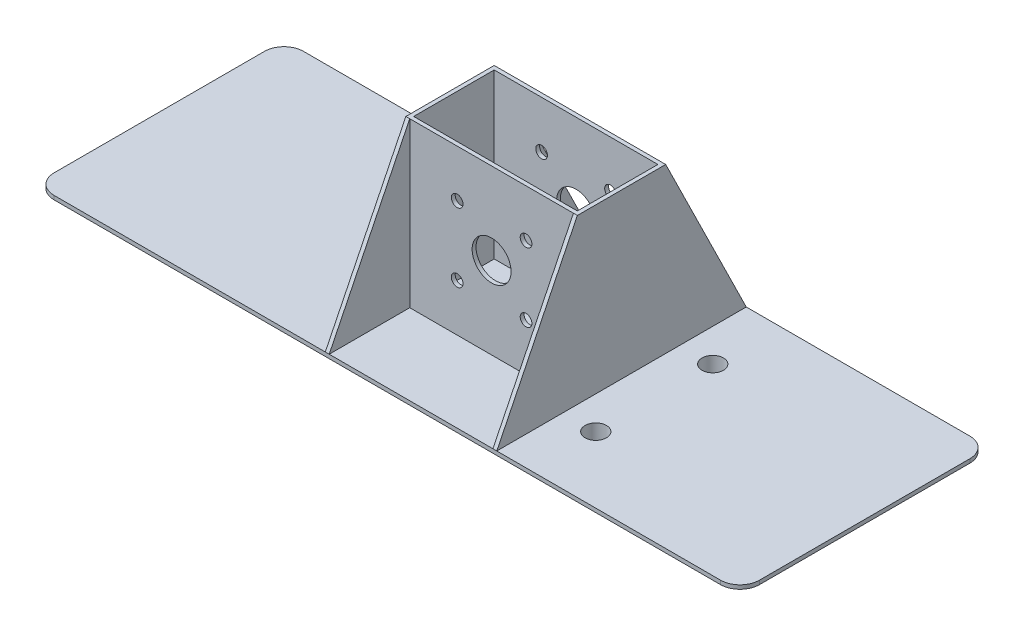
SolidWorks part; units mm, degrees
material "ABS"
ref_plane "Front Plane" through (0, 0, 0) normal (0, 0, 1) x (1, 0, 0)
ref_plane "Top Plane" through (0, 0, 0) normal (0, 1, 0) x (1, 0, 0)
ref_plane "Right Plane" through (0, 0, 0) normal (1, 0, 0) x (0, 0, -1)
sketch "Sketch1" plane through (0, 0, 0) normal (0, 1, 0) x (1, 0, 0)
  line L1 (85.5, 32) -> (-85.5, 32)
  line L2 (90.5, 27) -> (90.5, -27)
  line L3 (85.5, -32) -> (-85.5, -32)
  line L4 (-90.5, 27) -> (-90.5, -27)
  line L5 (90.5, 32) -> (-90.5, -32) construction
  line L6 (90.5, -32) -> (-90.5, 32) construction
  arc A0 (85.5, 32) -> (90.5, 27) centre (85.5, 27) cw
  arc A1 (90.5, -27) -> (85.5, -32) centre (85.5, -27) cw
  arc A2 (-85.5, -32) -> (-90.5, -27) centre (-85.5, -27) cw
  arc A3 (-85.5, 32) -> (-90.5, 27) centre (-85.5, 27) ccw
  point P0 (0, 0)
  dimension "D1" = 5
  dimension "D2" = 181
  dimension "D3" = 64
extrude "Boss-Extrude1" add sketch "Sketch1" along normal blind 1
sketch "Sketch2" plane through (0, 1, 0) normal (0, 1, 0) x (1, 0, 0)
  line L0 (-90.5, 0) -> (90.5, 0) construction
  line L1 (-90.5, 27) -> (-90.5, -27) construction
  line L2 (90.5, -27) -> (90.5, 27) construction
  circle A0 centre (36.5, -15) radius 2.75
  circle A1 centre (36.5, 15) radius 2.75
  circle A2 centre (-25.5, 0) radius 2.75
  dimension "D1" = 30
  dimension "D3" = 5.5
  dimension "D4" = 62
  dimension "D2" = 127
extrude "Cut-Extrude1" cut sketch "Sketch2" against normal through all
sketch "Sketch9" plane through (0, 0, 0) normal (0, -1, 0) x (1, 0, 0)
  circle A0 centre (-25.5, 0) radius 4.75
  circle A1 centre (36.5, -15) radius 4.75
  circle A2 centre (36.5, 15) radius 4.75
  circle A3 centre (-25.5, 0) radius 2.75
  circle A4 centre (36.5, 15) radius 2.75
  circle A5 centre (36.5, -15) radius 2.75
  dimension "D1" = 9.5
  dimension "D2" = 9.5
  dimension "D3" = 9.5
extrude "Boss-Extrude4" add sketch "Sketch9" along normal blind 6.5
sketch "Sketch11" plane through (0, 1, 0) normal (0, 1, 0) x (1, 0, 0)
  line L0 (85.5, 32) -> (-85.5, 32) construction
  line L1 (-15.9, 32) -> (-14.9, 32)
  line L2 (-15.9, 32) -> (-15.9, -32)
  line L3 (-15.9, -32) -> (-14.9, -32)
  line L4 (28.1, 32) -> (28.1, -32)
  line L5 (-85.5, -32) -> (85.5, -32) construction
  line L6 (-14.9, 10.3333) -> (27.1, -10.3333) construction
  line L7 (27.1, 32) -> (28.1, 32)
  line L8 (-13.9, 0) -> (26.1, 0) construction
  line L9 (-14.9, 10.3333) -> (27.1, 10.3333)
  line L10 (-14.9, 10.3333) -> (-14.9, -10.3333)
  line L11 (-14.9, -10.3333) -> (27.1, -10.3333)
  line L12 (27.1, 10.3333) -> (27.1, -10.3333)
  line L14 (-14.9, 32) -> (-14.9, 11.3333)
  line L15 (-14.9, 11.3333) -> (27.1, 11.3333)
  line L16 (27.1, 32) -> (27.1, 11.3333)
  line L18 (-14.9, -32) -> (-14.9, -11.3333)
  line L19 (-14.9, -11.3333) -> (27.1, -11.3333)
  line L20 (27.1, -32) -> (27.1, -11.3333)
  line L21 (27.1, -32) -> (28.1, -32)
  point P12 (6.1, 0)
  point P14 (6.1, 0)
  point P21 (27.1, 0)
  point P22 (28.1, 0)
  dimension "D1" = 42
  dimension "D2" = 1
  dimension "D3" = 1
  dimension "D4" = 1
  dimension "D5" = 14.9
extrude "Boss-Extrude6" add sketch "Sketch11" along normal blind 42
sketch "Sketch12" plane through (-14.9, 0, 0) normal (1, 0, 0) x (0, 0, -1)
  line L0 (-11.3333, 43) -> (-32, 1)
  line L1 (-32, 1) -> (-32, 43)
  line L2 (-32, 43) -> (-11.3333, 43)
  line L3 (11.3333, 43) -> (32, 1)
  line L4 (32, 1) -> (32, 43)
  line L5 (32, 43) -> (11.3333, 43)
extrude "Cut-Extrude2" cut sketch "Sketch12" against normal through all both and the other way through all
sketch "Sketch13" plane through (0, 0, 11.3333) normal (0, 0, 1) x (1, 0, 0)
  line L0 (-14.9, 22) -> (27.1, 22) construction
  line L1 (6.1, 22) -> (6.1, 43) construction
  line L2 (-14.9, 43) -> (27.1, 43) construction
  line L3 (-14.9, 43) -> (-14.9, 1) construction
  line L6 (-2.7388, 13.1612) -> (6.1, 22) construction
  line L7 (27.1, 1) -> (27.1, 43) construction
  circle A0 centre (6.1, 22) radius 5
  circle A1 centre (-2.7388, 13.1612) radius 1.5
  circle A2 centre (-2.7388, 30.8388) radius 1.5
  circle A3 centre (14.9388, 13.1612) radius 1.5
  circle A4 centre (14.9388, 30.8388) radius 1.5
  dimension "D1" = 10
  dimension "D2" = 12.5
  dimension "D3" = 3
  dimension "D4" = 45
extrude "Cut-Extrude3" cut sketch "Sketch13" against normal through all both
